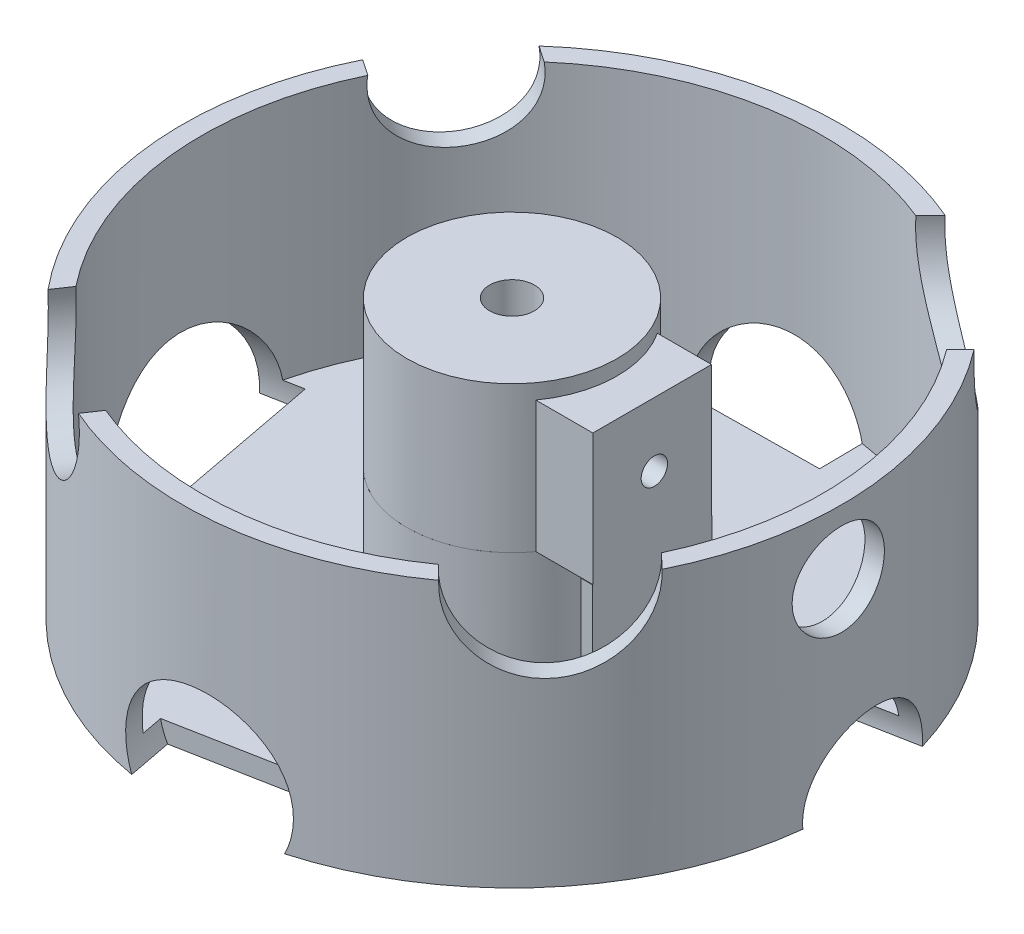
SolidWorks part; units mm, degrees
ref_plane "Front Plane" through (0, 0, 0) normal (0, 0, 1) x (1, 0, 0)
ref_plane "Top Plane" through (0, 0, 0) normal (0, 1, 0) x (1, 0, 0)
ref_plane "Right Plane" through (0, 0, 0) normal (1, 0, 0) x (0, 0, -1)
sketch "Sketch1" plane through (0, 0, 0) normal (0, 1, 0) x (1, 0, 0)
  circle A0 centre (0, 0) radius 15.958
extrude "ShaftHolderNearMotor" add sketch "Sketch1" along normal blind 22.19
sketch "Sketch2" plane through (0, 22.19, 0) normal (0, 1, 0) x (1, 0, 0)
  circle A0 centre (0, 0) radius 3.4
extrude "Cut-Extrude1" cut sketch "Sketch2" against normal blind 13.55 contours A0
ref_plane "Plane1" through (0, 20.45, 0) normal (0, 1, 0) x (1, 0, 0)
ref_axis "Axis1" through (0, 8.64, 0) along (0, 1, 0)
ref_point "Point2"
sketch "Sketch5" plane through (0, 20.45, 0) normal (0, 1, 0) x (1, 0, 0)
  line L0 (0, 0) -> (2.6, 0) construction
  line L2 (2.6, -3.5716) -> (4.1507, -3.5716)
  line L3 (2.6, -3.5716) -> (2.6, 3.6126)
  line L4 (2.6, 3.6126) -> (4.1507, 3.6126)
  line L5 (4.1507, -3.5716) -> (4.1507, 3.6126)
extrude "Boss-Extrude2" add sketch "Sketch5" against normal blind 13.55
sketch "Sketch7" plane through (2.6, 0, 0) normal (-1, 0, 0) x (0, 0, 1)
  line L1 (-8.6717, 19.91) -> (9.3323, 19.91)
  line L2 (-8.6717, 19.91) -> (-8.6717, 0)
  line L3 (-8.6717, 0) -> (9.3323, 0)
  line L4 (9.3323, 19.91) -> (9.3323, 0)
extrude "Boss-Extrude3" add sketch "Sketch7" against normal blind 19
sketch "Sketch6" plane through (2.6, 0, 0) normal (-1, 0, 0) x (0, 0, 1)
  line L1 (-2.1909, 8.64) -> (-2.1909, 20.45) construction
  line L2 (2.1909, 20.45) -> (2.1909, 8.64) construction
  line L3 (-2.1909, 15.4522) -> (2.1909, 15.4522) construction
  circle A0 centre (0, 10.2369) radius 2
extrude "Cut-Extrude2" cut sketch "Sketch6" against normal up to surface (19 mm away) and the other way blind 1 up to face at (21.6, 9.955, 0.3303)
ref_axis "Axis2" through (-1.8994, 10.2369, 0) along (-1, 0, 0)
ref_axis "Axis4" through (21.6, 10.2369, 0) along (-1, 0, 0)
ref_plane "Plane3" through (0, 0, 0) normal (0, 0, 1) x (1, 0, 0)
sketch "Sketch9" plane through (0, 0, 0) normal (0, 0, 1) x (1, 0, 0)
  line L0 (11.8765, 10.2369) -> (11.8765, 5.8619)
  line L1 (4.9434, 5.8619) -> (11.8765, 5.8619)
  line L2 (4.9434, 5.8619) -> (4.9434, 10.2369)
  line L3 (4.9434, 10.2369) -> (4.9434, 14.6143)
  line L4 (4.9434, 14.6143) -> (11.8765, 14.6143)
  line L5 (11.8765, 14.6143) -> (11.8765, 10.2369)
  line L6 (21.6, 10.2369) -> (1.6, 10.2369) construction
  line L7 (4.9434, 14.6143) -> (11.8765, 5.8619) construction
extrude "NutOpening" cut sketch "Sketch9" against normal blind 30
sketch "Sketch10" plane through (0, 0, 0) normal (0, -1, 0) x (1, 0, 0)
  circle A0 centre (0, 0) radius 50
extrude "Boss-Extrude4" add sketch "Sketch10" along normal blind 20
sketch "Sketch11" plane through (0, 0, 0) normal (0, 1, 0) x (1, 0, 0)
  line L1 (31.7817, 38.8528) -> (14.4942, 48.0577) construction
  line L2 (14.4942, 48.0577) -> (-5, 49.9462) construction
  line L3 (-5, 49.9462) -> (-23.733, 44.2308) construction
  line L4 (-23.733, 44.2308) -> (-38.8528, 31.7817) construction
  line L5 (-38.8528, 31.7817) -> (-48.0577, 14.4942) construction
  line L6 (-48.0577, 14.4942) -> (-49.9462, -5) construction
  line L7 (-49.9462, -5) -> (-44.2308, -23.733) construction
  line L8 (-44.2308, -23.733) -> (-31.7817, -38.8528) construction
  line L9 (-31.7817, -38.8528) -> (-14.4942, -48.0577) construction
  line L10 (-14.4942, -48.0577) -> (5, -49.9462) construction
  line L11 (5, -49.9462) -> (23.733, -44.2308) construction
  line L12 (23.733, -44.2308) -> (38.8528, -31.7817) construction
  line L13 (38.8528, -31.7817) -> (48.0577, -14.4942) construction
  line L14 (48.0577, -14.4942) -> (49.9462, 5) construction
  line L15 (49.9462, 5) -> (44.2308, 23.733) construction
  line L16 (44.2308, 23.733) -> (31.7817, 38.8528) construction
  circle A0 centre (0, 0) radius 49.2313 construction
  circle A1 centre (5, -49.9462) radius 5
  circle A2 centre (-14.4942, -48.0577) radius 5
  circle A3 centre (-31.7817, -38.8528) radius 5
  circle A4 centre (-44.2308, -23.733) radius 5
  circle A5 centre (-49.9462, -5) radius 5
  circle A6 centre (-48.0577, 14.4942) radius 5
  circle A7 centre (-38.8528, 31.7817) radius 5
  circle A8 centre (-23.733, 44.2308) radius 5
  circle A9 centre (-5, 49.9462) radius 5
  circle A10 centre (14.4942, 48.0577) radius 5
  circle A11 centre (31.7817, 38.8528) radius 5
  circle A12 centre (44.2308, 23.733) radius 5
  circle A13 centre (49.9462, 5) radius 5
  circle A14 centre (48.0577, -14.4942) radius 5
  circle A15 centre (38.8528, -31.7817) radius 5
  circle A16 centre (23.733, -44.2308) radius 5
sketch "Sketch12" plane through (0, 0, 0) normal (0, 1, 0) x (1, 0, 0)
  circle A0 centre (0, 0) radius 47.0828
  circle A1 centre (0, 0) radius 15.9579
extrude "CutToRemveExcessMaterial" cut sketch "Sketch12" against normal offset from surface (17 mm away) 3 up to face at (0, -20, -50)
sketch "Sketch13" plane through (0, 0, 0) normal (0, 1, 0) x (1, 0, 0)
  circle A0 centre (0, 0) radius 47.0828
  circle A1 centre (0, 0) radius 50
extrude "Boss-Extrude5" add sketch "Sketch13" along normal blind 20
sketch "Sketch14" plane through (11.8765, 0, 0) normal (-1, 0, 0) x (0, 0, 1)
  line L1 (-5.0541, 10.2369) -> (-2.5271, 5.8599)
  line L2 (-2.5271, 5.8599) -> (2.5271, 5.8599)
  line L3 (2.5271, 5.8599) -> (5.0541, 10.2369)
  line L4 (5.0541, 10.2369) -> (2.5271, 14.6139)
  line L5 (2.5271, 14.6139) -> (-2.5271, 14.6139)
  line L6 (-2.5271, 14.6139) -> (-5.0541, 10.2369)
  circle A0 centre (0, 10.2369) radius 4.377 construction
extrude "Cut-Extrude6" cut sketch "Sketch14" along normal up to surface (6.9331 mm away) up to face at (4.9434, 10.2377, -5.391)
sketch "Sketch16" plane through (21.6, 0, 0) normal (1, 0, 0) x (0, 0, -1)
  circle A0 centre (0, 10.2369) radius 7
extrude "Cut-Extrude7" cut sketch "Sketch16" along normal blind 40
ref_plane "Plane4" through (-0.571, 0, -49.9967) normal (-0.0114, 0, -0.9999) x (-0.9999, 0, 0.0114)
ref_plane "Plane5" through (-27.4359, 0, -41.8004) normal (-0.5487, 0, -0.836) x (-0.836, 0, 0.5487)
sketch "Sketch17" plane through (-0.571, 0, -49.9967) normal (-0.0114, 0, -0.9999) x (-0.9999, 0, 0.0114)
  line L1 (-6.9779, 26.3682) -> (19.0025, 26.3682)
sketch "Sketch18" plane through (-27.4359, 0, -41.8004) normal (-0.5487, 0, -0.836) x (-0.836, 0, 0.5487)
  line L1 (2.3429, -8.8145) -> (-7.3736, -8.8145)
  line L2 (2.3429, -8.8145) -> (2.3429, -36.514)
  line L3 (2.3429, -36.514) -> (-7.3736, -36.514)
  line L4 (-7.3736, -8.8145) -> (-7.3736, -36.514)
ref_plane "Plane6" through (18.6054, 0, -46.4095) normal (0.3721, 0, -0.9282) x (-0.9282, 0, -0.3721)
ref_plane "Plane7" through (34.9493, 0, -35.7568) normal (0.699, 0, -0.7151) x (-0.7151, 0, -0.699)
ref_plane "Plane8" through (45.9725, 0, -19.6605) normal (0.9194, 0, -0.3932) x (-0.3932, 0, -0.9194)
ref_plane "Plane9" through (49.1178, 0, -9.3511) normal (0.9824, 0, -0.187) x (-0.187, 0, -0.9824)
ref_plane "Plane10" through (46.4095, 0, 18.6054) normal (0.9282, 0, 0.3721) x (0.3721, 0, -0.9282)
ref_plane "Plane11" through (35.7568, 0, 34.9493) normal (0.7151, 0, 0.699) x (0.699, 0, -0.7151)
ref_plane "Plane12" through (9.3511, 0, 49.1178) normal (0.187, 0, 0.9824) x (0.9824, 0, -0.187)
ref_plane "Plane13" through (-28.1193, 0, 41.3438) normal (-0.5624, 0, 0.8269) x (0.8269, 0, 0.5624)
ref_plane "Plane14" through (-49.1178, 0, 9.3511) normal (-0.9824, 0, 0.187) x (0.187, 0, 0.9824)
ref_plane "Plane15" through (-41.3438, 0, -28.1193) normal (-0.8269, 0, -0.5624) x (-0.5624, 0, 0.8269)
sketch "Sketch19" plane through (9.3511, 0, 49.1178) normal (0.187, 0, 0.9824) x (0.9824, 0, -0.187)
  circle A0 centre (-6.5538, -15.0444) radius 12
  point P2 (-6.5538, -15.0444)
extrude "Cut-Extrude8" cut sketch "Sketch19" against normal blind 10
sketch "Sketch20" plane through (35.7568, 0, 34.9493) normal (0.7151, 0, 0.699) x (0.699, 0, -0.7151)
  circle A0 centre (3.5584, 19.4292) radius 12
extrude "Cut-Extrude9" cut sketch "Sketch20" against normal blind 10
sketch "Sketch21" plane through (49.1178, 0, -9.3511) normal (0.9824, 0, -0.187) x (-0.187, 0, -0.9824)
  circle A0 centre (-4.7912, -19.2219) radius 10
  point P2 (-4.7912, -19.2219)
sketch "Sketch22" plane through (34.9493, 0, -35.7568) normal (0.699, 0, -0.7151) x (-0.7151, 0, -0.699)
  circle A0 centre (5.4277, 18.4908) radius 12.5535
  point P2 (5.4277, 18.4908)
extrude "Cut-Extrude10" cut sketch "Sketch22" against normal blind 10
extrude "Cut-Extrude11" cut sketch "Sketch21" against normal blind 10 contours A0
sketch "Sketch23" plane through (-0.571, 0, -49.9967) normal (-0.0114, 0, -0.9999) x (-0.9999, 0, 0.0114)
  circle A0 centre (4.5252, -20.0178) radius 11.9653
  point P2 (4.5252, -20.0178)
extrude "Cut-Extrude12" cut sketch "Sketch23" against normal blind 10
sketch "Sketch25" plane through (-41.3438, 0, -28.1193) normal (-0.8269, 0, -0.5624) x (-0.5624, 0, 0.8269)
  circle A0 centre (-2.6498, 18.6432) radius 9.6297
  point P2 (-2.6498, 18.6432)
extrude "Cut-Extrude13" cut sketch "Sketch25" against normal blind 10
sketch "Sketch26" plane through (-49.1178, 0, 9.3511) normal (-0.9824, 0, 0.187) x (0.187, 0, 0.9824)
  circle A0 centre (-4.4977, -19.1264) radius 15.0124
  point P2 (-4.4977, -19.1264)
extrude "Cut-Extrude14" cut sketch "Sketch26" against normal blind 10
sketch "Sketch27" plane through (-28.1193, 0, 41.3438) normal (-0.5624, 0, 0.8269) x (0.8269, 0, 0.5624)
  circle A0 centre (-2.2875, 17.6222) radius 11.8547
  point P2 (-2.2875, 17.6222)
extrude "Cut-Extrude15" cut sketch "Sketch27" against normal blind 10
sketch "Sketch28" plane through (0, 0, 0) normal (0, -1, 0) x (1, 0, 0)
  line L1 (19.8832, 9.4042) -> (21.6, 9.4042)
  line L2 (19.8832, 9.4042) -> (19.8832, -8.7683)
  line L3 (19.8832, -8.7683) -> (21.6, -8.7683)
  line L4 (21.6, 9.4042) -> (21.6, -8.7683)
extrude "Boss-Extrude6" add sketch "Sketch28" along normal up to surface (17 mm away) up to face at (-0.493, -17, 0.1034)
